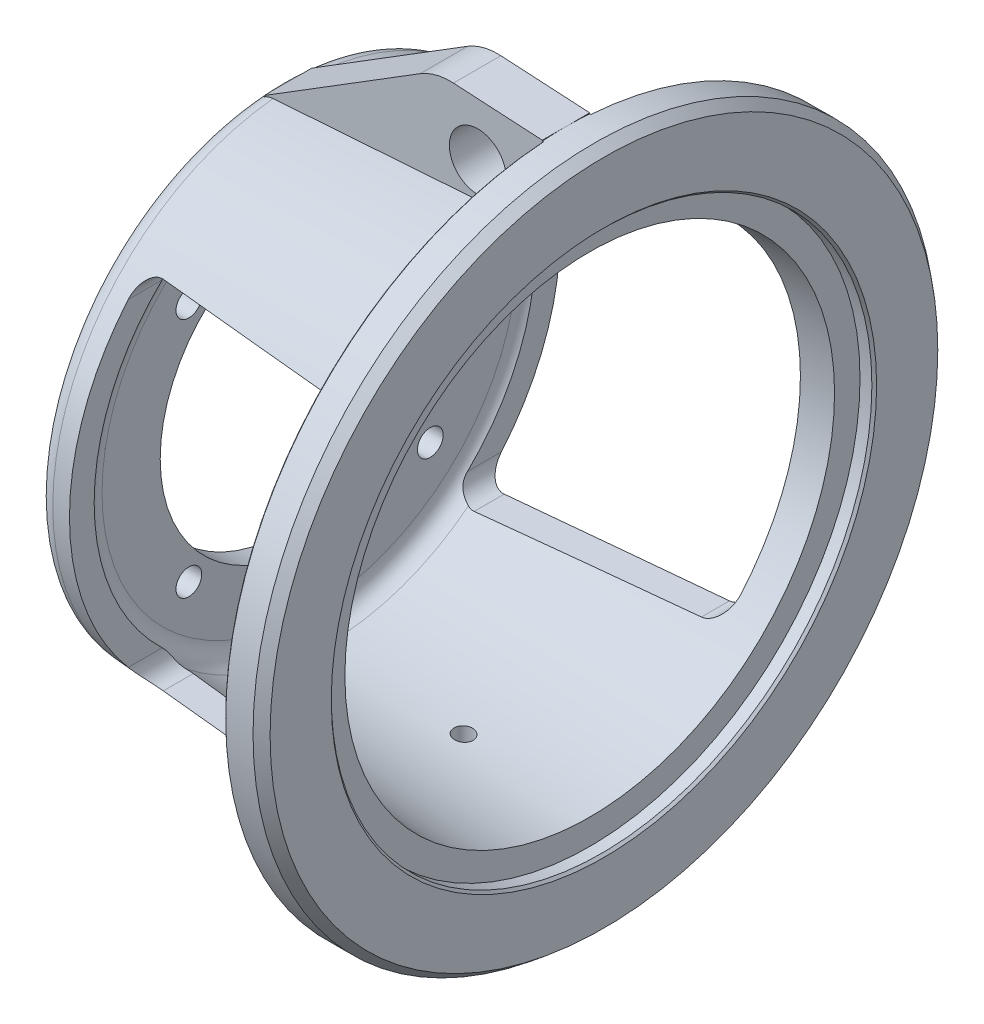
SolidWorks part; units mm, degrees
material "CD4Mc-U Duplex Stainless Steel"
ref_plane "Front Plane" through (0, 0, 0) normal (0, 0, 1) x (1, 0, 0)
ref_plane "Top Plane" through (0, 0, 0) normal (0, 1, 0) x (1, 0, 0)
ref_plane "Right Plane" through (0, 0, 0) normal (1, 0, 0) x (0, 0, -1)
sketch "Sketch2" plane through (0, 0, 0) normal (0, 0, 1) x (1, 0, 0)
  line L0 (0, 0) -> (151.2672, 0) construction
  line L1 (0, 0) -> (0, 150.7291)
  line L2 (11.8141, 163.3982) -> (180.2099, 175.1736)
  line L3 (192.024, 187.8426) -> (192.024, 228.6)
  line L4 (192.024, 228.6) -> (217.424, 228.6)
  line L5 (217.424, 228.6) -> (217.424, 180.975)
  line L6 (207.899, 163.9269) -> (32.1595, 151.638)
  line L7 (20.3454, 138.9689) -> (20.3454, 0)
  line L8 (0, 0) -> (20.3454, 0)
  line L9 (11.8141, 163.3982) -> (206.3963, 163.3982) construction
  line L10 (217.424, 180.975) -> (207.899, 180.975)
  line L11 (207.899, 180.975) -> (207.899, 163.9269)
  arc A0 (0, 150.7291) -> (11.8141, 163.3982) centre (12.7, 150.7291) cw
  arc A1 (180.2099, 175.1736) -> (192.024, 187.8426) centre (179.324, 187.8426) ccw
  arc A2 (32.1595, 151.638) -> (20.3454, 138.9689) centre (33.0454, 138.9689) ccw
  dimension "D1" = 12.7
  dimension "D2" = 163.3982
  dimension "D3" = 151.638
  dimension "D4" = 20.3454
  dimension "D5" = 4
  dimension "D6" = 25.4
  dimension "D7" = 228.6
  dimension "D8" = 217.424
  dimension "D9" = 180.975
  dimension "D10" = 9.525
revolve "Revolve1" add sketch "Sketch2" angle 360 about L0
sketch "Sketch3" plane through (0, 0, 0) normal (-1, 0, 0) x (0, 0, 1)
  circle A0 centre (0, 0) radius 133.35
  dimension "D1" = 266.7
extrude "Cut-Extrude1" cut sketch "Sketch3" against normal blind 4.7752
sketch "Sketch4" plane through (4.7752, 0, 0) normal (-1, 0, 0) x (0, 0, 1)
  circle A0 centre (0, 0) radius 100.0125
  dimension "D1" = 200.025
extrude "Cut-Extrude2" cut sketch "Sketch4" against normal up to next
sketch "Sketch5" plane through (217.424, 0, 0) normal (1, 0, 0) x (0, 0, -1)
  circle A0 centre (0, 0) radius 180.9763
  dimension "D1" = 361.9525
extrude "Cut-Extrude3" cut sketch "Sketch5" against normal blind 9.525
sketch "Sketch6" plane through (4.7752, 0, 0) normal (-1, 0, 0) x (0, 0, 1)
  line L0 (0, 0) -> (114.3, 0) construction
  line L1 (0, 0) -> (80.8223, 80.8223) construction
  circle A0 centre (0, 0) radius 114.3 construction
  circle A1 centre (80.8223, 80.8223) radius 8.636
  point P3 (80.8223, 80.8223)
  dimension "D1" = 228.6
  dimension "D3" = 17.272
  dimension "D2" = 45
extrude "Cut-Extrude4" cut sketch "Sketch6" against normal up to next
pattern_circular "CirPattern1" count 4 over 360 about axis through (4.7752, 0, 0) along (-1, 0, 0) of "Cut-Extrude4"
sketch "Sketch7" plane through (217.424, 0, 0) normal (1, 0, 0) x (0, 0, -1)
  line L0 (0, 0) -> (206.375, 0) construction
  line L1 (0, 0) -> (199.3429, 53.4138) construction
  circle A0 centre (0, 0) radius 206.375 construction
  circle A1 centre (199.3429, 53.4138) radius 11.1125
  dimension "D1" = 412.75
  dimension "D3" = 22.225
  dimension "D2" = 15
extrude "Cut-Extrude5" [suppressed] cut sketch "Sketch7" against normal up to next
pattern_circular "CirPattern2" [suppressed] count 12 over 360 of bodies 107
sketch "Sketch8" plane through (0, 0, 0) normal (0, 0, 1) x (1, 0, 0)
  line L0 (192.024, 228.6) -> (192.024, -228.6) construction
  line L1 (192.024, 228.6) -> (192.024, 173.461)
  line L2 (5.9873, 161.5101) -> (110.2718, 226.302)
  line L3 (192.024, 228.6) -> (132.5388, 231.9782)
  line L4 (192.024, 173.461) -> (5.4488, 158.5456)
  line L5 (5.4488, 158.5456) -> (5.9873, 161.5101)
  line L6 (192.024, 228.6) -> (192.024, 173.461)
  arc A0 (11.8141, 163.3982) -> (0, 150.7291) centre (12.7, 150.7291) ccw construction
  arc A1 (132.5388, 231.9782) -> (110.2718, 226.302) centre (130.3786, 193.9395) ccw
  dimension "D1" = 76.2
  dimension "D2" = 231.9782
extrude "Boss-Extrude1" add sketch "Sketch8" along normal mid plane 31.75 contours L3 A1 L2 L5 L4 L1 region at (119.8434, 193.7127, 0)
sketch "Sketch9" plane through (0, 0, 15.875) normal (0, 0, 1) x (1, 0, 0)
  line L0 (217.424, -228.6) -> (217.424, 228.6) construction
  circle A0 centre (148.844, 194.564) radius 19.05
  dimension "D1" = 38.1
  dimension "D2" = 68.58
  dimension "D3" = 194.564
extrude "Cut-Extrude6" cut sketch "Sketch9" against normal up to next
sketch "Sketch10" plane through (0, 0, 0) normal (0, 1, 0) x (1, 0, 0)
  line L0 (217.424, -228.6) -> (217.424, 228.6) construction
  circle A0 centre (123.444, 0) radius 6.35
  dimension "D2" = 12.7
  dimension "D1" = 93.98
extrude "Cut-Extrude7" cut sketch "Sketch10" against normal up to next
sketch "Sketch11" plane through (0, 0, 0) normal (0, 0, 1) x (1, 0, 0)
  line L0 (0, 150.7291) -> (0, -150.7291) construction
  line L1 (36.5252, -119.3419) -> (173.8376, -119.3419)
  line L2 (23.8252, -106.6419) -> (23.8252, 106.6419)
  line L3 (36.5252, 119.3419) -> (173.8376, 119.3419)
  line L4 (186.5376, -106.6419) -> (186.5376, 106.6419)
  line L5 (23.8252, -119.3419) -> (186.5376, 119.3419) construction
  line L6 (23.8252, 119.3419) -> (186.5376, -119.3419) construction
  arc A0 (36.5252, -119.3419) -> (23.8252, -106.6419) centre (36.5252, -106.6419) cw
  arc A1 (173.8376, -119.3419) -> (186.5376, -106.6419) centre (173.8376, -106.6419) ccw
  arc A2 (173.8376, 119.3419) -> (186.5376, 106.6419) centre (173.8376, 106.6419) cw
  arc A3 (23.8252, 106.6419) -> (36.5252, 119.3419) centre (36.5252, 106.6419) cw
  point P0 (105.1814, 0)
  dimension "D4" = 12.7
  dimension "D1" = 162.7124
  dimension "D2" = 238.6838
  dimension "D3" = 23.8252
extrude "Cut-Extrude8" cut sketch "Sketch11" against normal through all both and the other way through all
chamfer "Chamfer1" distance 1.5875 angle 45 1 edges at (217.424, 0, -180.9763)
chamfer "Chamfer2" distance 0.7937 angle 45 1 edges at (192.024, -228.6, 0)
ref_axis "Axis1" through (148.844, 194.564, -15.875) along (0, 0, 1)
ref_axis "Axis2" through (123.444, -172.0095, 0) along (0, 1, 0)
sketch "Sketch12" plane through (217.424, 0, 0) normal (1, 0, 0) x (0, 0, -1)
  circle A0 centre (0, 0) radius 180.975
chamfer "Chamfer4" distance 5.08 distance2 6.35 1 edges at (217.424, 0, 228.6) first distance on face at (217.424, 0, 182.5638)
